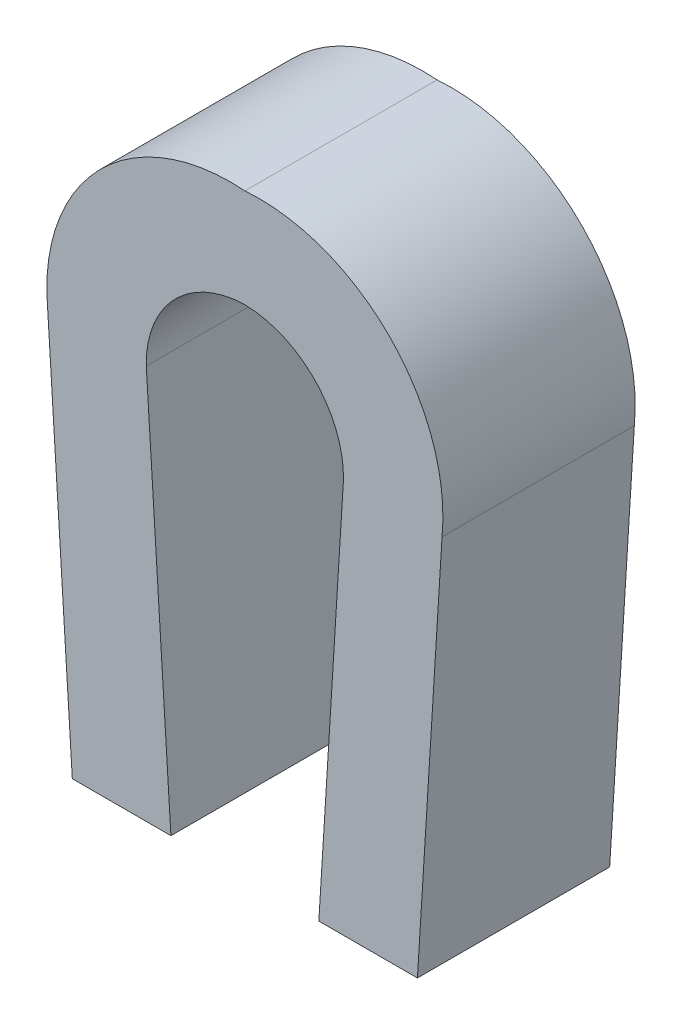
SolidWorks part; units mm, degrees
ref_plane "Front Plane" through (0, 0, 0) normal (0, 0, 1) x (1, 0, 0)
ref_plane "Top Plane" through (0, 0, 0) normal (0, 1, 0) x (1, 0, 0)
ref_plane "Right Plane" through (0, 0, 0) normal (1, 0, 0) x (0, 0, -1)
sketch "Sketch1" plane through (0, 0, 0) normal (0, 0, 1) x (1, 0, 0)
  line L0 (-2, 4) -> (-1.5, -4)
  line L5 (-1.5, -4) -> (-3.5, -4)
  line L6 (-3.5, -4) -> (-4, 4)
  line L10 (0, 7.8443) -> (0, -6.8113) construction
  line L11 (3.5, -4) -> (4, 4)
  line L12 (1.5, -4) -> (3.5, -4)
  line L13 (2, 4) -> (1.5, -4)
  arc A4 (-2, 4) -> (0, 6.0772) centre (0.036, 4.0411) cw
  arc A5 (-4, 4) -> (0, 8.0772) centre (-0.2889, 4.3599) cw
  arc A6 (4, 4) -> (0, 8.0772) centre (0.2889, 4.3599) ccw
  arc A7 (2, 4) -> (0, 6.0772) centre (-0.036, 4.0411) ccw
  dimension "D1" = 8
  dimension "D2" = 2
  dimension "D3" = 2
  dimension "D4" = 2
  dimension "D6" = 1.5
extrude "Boss-Extrude1" add sketch "Sketch1" along normal blind 3.9
